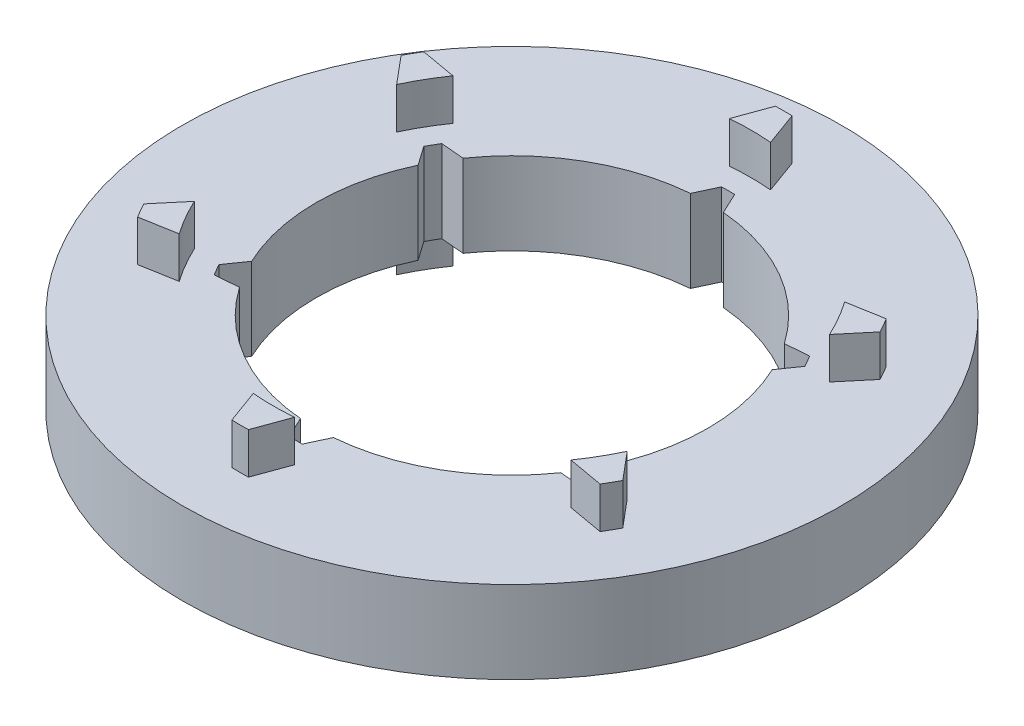
SolidWorks part; units mm, degrees
ref_plane "Front Plane" through (0, 0, 0) normal (0, 0, 1) x (1, 0, 0)
ref_plane "Top Plane" through (0, 0, 0) normal (0, 1, 0) x (1, 0, 0)
ref_plane "Right Plane" through (0, 0, 0) normal (1, 0, 0) x (0, 0, -1)
sketch "Sketch1" plane through (0, 0, 0) normal (0, 1, 0) x (1, 0, 0)
  line L0 (0, 0) -> (0, 34.5685) construction
  line L1 (-2, 26.1737) -> (-2, 23.6656) construction
  line L2 (-2, 23.6656) -> (-0.8006, 26.2378)
  line L3 (2, 23.6656) -> (0.8006, 26.2378)
  line L4 (19.495, 13.5649) -> (22.3223, 13.8122)
  line L5 (21.495, 10.1008) -> (23.1229, 12.4256)
  line L6 (21.495, -10.1008) -> (23.1229, -12.4256)
  line L7 (19.495, -13.5649) -> (22.3223, -13.8122)
  line L8 (2, -23.6656) -> (0.8006, -26.2378)
  line L9 (-2, -23.6656) -> (-0.8006, -26.2378)
  line L10 (-19.495, -13.5649) -> (-22.3223, -13.8122)
  line L11 (-21.495, -10.1008) -> (-23.1229, -12.4256)
  line L12 (-21.495, 10.1008) -> (-23.1229, 12.4256)
  line L13 (-19.495, 13.5649) -> (-22.3223, 13.8122)
  arc A0 (-2, 23.6656) -> (-19.495, 13.5649) centre (0, 0) ccw
  arc A1 (0.8006, 26.2378) -> (-0.8006, 26.2378) centre (0, 0) ccw
  arc A2 (23.1229, 12.4256) -> (22.3223, 13.8122) centre (0, 0) ccw
  arc A3 (22.3223, -13.8122) -> (23.1229, -12.4256) centre (0, 0) ccw
  arc A4 (-0.8006, -26.2378) -> (0.8006, -26.2378) centre (0, 0) ccw
  arc A5 (-23.1229, -12.4256) -> (-22.3223, -13.8122) centre (0, 0) ccw
  arc A6 (-22.3223, 13.8122) -> (-23.1229, 12.4256) centre (0, 0) ccw
  arc A7 (-21.495, 10.1008) -> (-21.495, -10.1008) centre (0, 0) ccw
  arc A8 (19.495, 13.5649) -> (2, 23.6656) centre (0, 0) ccw
  arc A9 (21.495, -10.1008) -> (21.495, 10.1008) centre (0, 0) ccw
  arc A10 (2, -23.6656) -> (19.495, -13.5649) centre (0, 0) ccw
  arc A11 (-19.495, -13.5649) -> (-2, -23.6656) centre (0, 0) ccw
  circle A12 centre (0, 0) radius 40
  point P30 (0, 0)
  dimension "D1" = 47.5
  dimension "D2" = 52.5
  dimension "D6" = 80
  dimension "D3" = 2
  dimension "D4" = 25
  dimension "D5" = 6
extrude "Boss-Extrude1" add sketch "Sketch1" along normal blind 10
sketch "4,5,6" plane through (0, 10, 0) normal (0, 1, 0) x (1, 0, 0)
  line L0 (0, 23.5241) -> (0, 36.2824) construction
  line L1 (2.5, 35.9681) -> (2.5, 28.892) construction
  line L2 (2.5, 28.892) -> (1.0105, 32.9845)
  line L3 (-2.5, 28.892) -> (-1.0105, 32.9845)
  line L4 (23.7712, 16.6111) -> (28.0602, 17.3673)
  line L5 (26.2712, 12.281) -> (29.0707, 15.6172)
  line L6 (26.2712, -12.281) -> (29.0707, -15.6172)
  line L7 (23.7712, -16.6111) -> (28.0602, -17.3673)
  line L8 (2.5, -28.892) -> (1.0105, -32.9845)
  line L9 (-2.5, -28.892) -> (-1.0105, -32.9845)
  line L10 (-23.7712, -16.6111) -> (-28.0602, -17.3673)
  line L11 (-26.2712, -12.281) -> (-29.0707, -15.6172)
  line L12 (-26.2712, 12.281) -> (-29.0707, 15.6172)
  line L13 (-23.7712, 16.6111) -> (-28.0602, 17.3673)
  arc A0 (2.5, 28.892) -> (-2.5, 28.892) centre (0, 0) ccw
  arc A1 (1.0105, 32.9845) -> (-1.0105, 32.9845) centre (0, 0) ccw
  arc A2 (26.2712, 12.281) -> (23.7712, 16.6111) centre (0, 0) ccw
  arc A3 (29.0707, 15.6172) -> (28.0602, 17.3673) centre (0, 0) ccw
  arc A4 (23.7712, -16.6111) -> (26.2712, -12.281) centre (0, 0) ccw
  arc A5 (28.0602, -17.3673) -> (29.0707, -15.6172) centre (0, 0) ccw
  arc A6 (-2.5, -28.892) -> (2.5, -28.892) centre (0, 0) ccw
  arc A7 (-1.0105, -32.9845) -> (1.0105, -32.9845) centre (0, 0) ccw
  arc A8 (-26.2712, -12.281) -> (-23.7712, -16.6111) centre (0, 0) ccw
  arc A9 (-29.0707, -15.6172) -> (-28.0602, -17.3673) centre (0, 0) ccw
  arc A10 (-23.7712, 16.6111) -> (-26.2712, 12.281) centre (0, 0) ccw
  arc A11 (-28.0602, 17.3673) -> (-29.0707, 15.6172) centre (0, 0) ccw
  point P31 (0, 0)
  dimension "D1" = 58
  dimension "D2" = 66
  dimension "D3" = 2.5
  dimension "D4" = 20
  dimension "D5" = 6
sketch "1,2,3" plane through (0, 10, 0) normal (0, 1, 0) x (1, 0, 0)
  line L0 (0, 18.8714) -> (0, 44.4172) construction
  line L1 (2.5, 34.9106) -> (2.5, 30.899) construction
  line L2 (2.5, 30.899) -> (1.0127, 34.9853)
  line L3 (-2.5, 30.899) -> (-1.0127, 34.9853)
  line L4 (25.5093, 17.6146) -> (29.7918, 18.3697)
  line L5 (28.0093, 13.2845) -> (30.8045, 16.6156)
  line L6 (28.0093, -13.2845) -> (30.8045, -16.6156)
  line L7 (25.5093, -17.6146) -> (29.7918, -18.3697)
  line L8 (2.5, -30.899) -> (1.0127, -34.9853)
  line L9 (-2.5, -30.899) -> (-1.0127, -34.9853)
  line L10 (-25.5093, -17.6146) -> (-29.7918, -18.3697)
  line L11 (-28.0093, -13.2845) -> (-30.8045, -16.6156)
  line L12 (-28.0093, 13.2845) -> (-30.8045, 16.6156)
  line L13 (-25.5093, 17.6146) -> (-29.7918, 18.3697)
  arc A0 (2.5, 30.899) -> (-2.5, 30.899) centre (0, 0) ccw
  arc A1 (1.0127, 34.9853) -> (-1.0127, 34.9853) centre (0, 0) ccw
  arc A2 (28.0093, 13.2845) -> (25.5093, 17.6146) centre (0, 0) ccw
  arc A3 (30.8045, 16.6156) -> (29.7918, 18.3697) centre (0, 0) ccw
  arc A4 (25.5093, -17.6146) -> (28.0093, -13.2845) centre (0, 0) ccw
  arc A5 (29.7918, -18.3697) -> (30.8045, -16.6156) centre (0, 0) ccw
  arc A6 (-2.5, -30.899) -> (2.5, -30.899) centre (0, 0) ccw
  arc A7 (-1.0127, -34.9853) -> (1.0127, -34.9853) centre (0, 0) ccw
  arc A8 (-28.0093, -13.2845) -> (-25.5093, -17.6146) centre (0, 0) ccw
  arc A9 (-30.8045, -16.6156) -> (-29.7918, -18.3697) centre (0, 0) ccw
  arc A10 (-25.5093, 17.6146) -> (-28.0093, 13.2845) centre (0, 0) ccw
  arc A11 (-29.7918, 18.3697) -> (-30.8045, 16.6156) centre (0, 0) ccw
  point P32 (0, 0)
  dimension "D1" = 62
  dimension "D2" = 70
  dimension "D3" = 2.5
  dimension "D4" = 20
  dimension "D5" = 6
extrude "Boss-Extrude6" add sketch "4,5,6" along normal blind 5
extrude "Boss-Extrude7" add sketch "4,5,6<2>" against normal blind 5 from surface starting at face at (0, 0, 40)
sketch "4,5,6<2>" plane through (0, 10, 0) normal (0, 1, 0) x (1, 0, 0) same geometry as "4,5,6"
